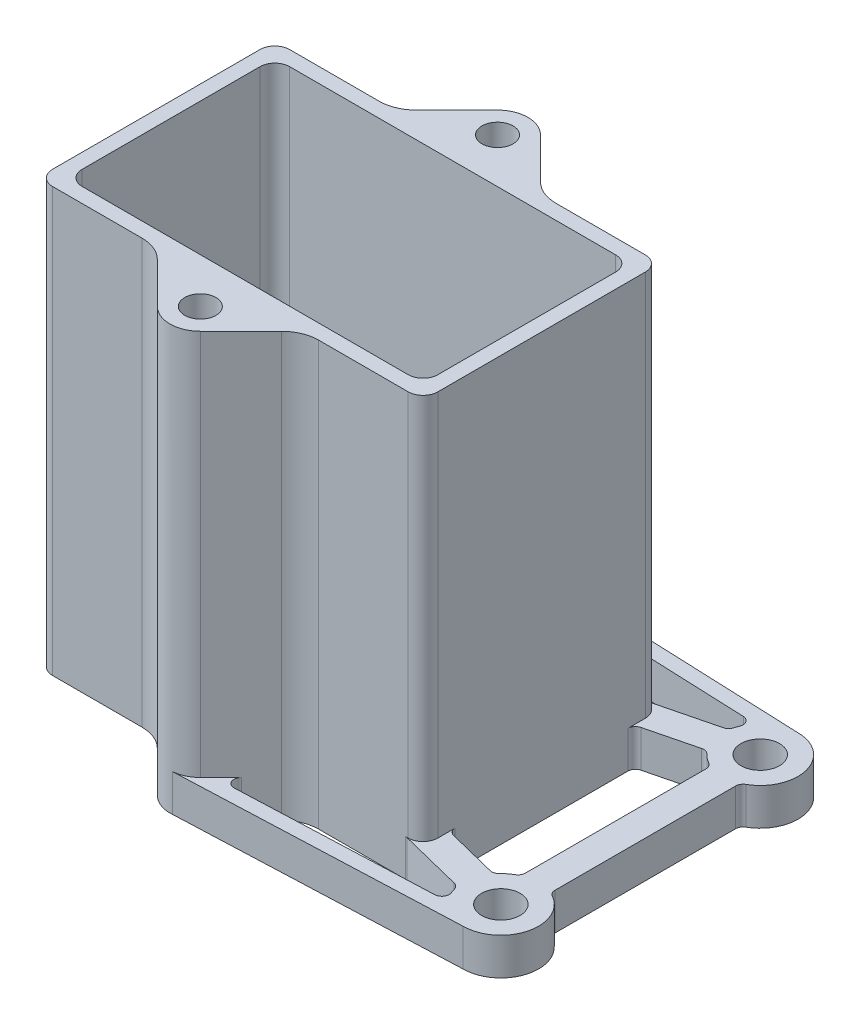
SolidWorks part; units mm, degrees
ref_plane "Front Plane" through (0, 0, 0) normal (0, 0, 1) x (1, 0, 0)
ref_plane "Top Plane" through (0, 0, 0) normal (0, 1, 0) x (1, 0, 0)
ref_plane "Right Plane" through (0, 0, 0) normal (1, 0, 0) x (0, 0, -1)
sketch "Sketch1" plane through (0, 0, 0) normal (0, 1, 0) x (1, 0, 0)
  line L1 (-26, -16) -> (26, -16)
  line L2 (-26, -16) -> (-26, 16)
  line L3 (-26, 16) -> (26, 16)
  line L4 (26, -16) -> (26, 16)
  line L5 (-26, -16) -> (26, 16) construction
  line L6 (-26, 16) -> (26, -16) construction
  point P0 (0, 0)
  dimension "D1" = 32
  dimension "D2" = 52
extrude "Boss-Extrude1" add sketch "Sketch1" along normal blind 3
sketch "Sketch2" plane through (0, 3, 0) normal (0, 1, 0) x (1, 0, 0)
  line L0 (24, -14) -> (24, 14)
  line L1 (24, 14) -> (-24, 14)
  line L2 (-24, 14) -> (-24, -14)
  line L3 (-24, -14) -> (24, -14)
  line L4 (26, -16) -> (26, 16)
  line L5 (26, 16) -> (-26, 16)
  line L6 (-26, 16) -> (-26, -16)
  line L7 (-26, -16) -> (26, -16)
  line L8 (26, -16) -> (26, 16)
  line L9 (26, 16) -> (-26, 16)
  line L10 (-26, 16) -> (-26, -16)
  line L11 (-26, -16) -> (26, -16)
  dimension "D1" = 0
  dimension "D2" = 2
extrude "Boss-Extrude2" add sketch "Sketch2" along normal blind 54.15
sketch "Sketch3" plane through (0, 0, 0) normal (0, 1, 0) x (1, 0, 0)
  line L0 (0, 0) -> (0, 20.05) construction
  line L1 (-2.8991, 22.9491) -> (-9.8483, 16)
  line L2 (-9.8483, 16) -> (9.8483, 16)
  line L3 (9.8483, 16) -> (2.8991, 22.9491)
  line L4 (26, -16) -> (26, 16)
  line L5 (-26, -16) -> (26, -16)
  line L6 (-26, 16) -> (-26, -16)
  line L7 (26, 16) -> (-26, 16)
  line L8 (26, -16) -> (26, 16)
  line L9 (-26, -16) -> (26, -16)
  line L10 (-26, 16) -> (-26, -16)
  line L11 (26, 16) -> (-26, 16)
  arc A0 (2.8991, 22.9491) -> (-2.8991, 22.9491) centre (0, 20.05) ccw
  circle A1 centre (0, 20.05) radius 2.1
  dimension "D3" = 2
  dimension "D4" = 4.2
  dimension "D2" = 45
  dimension "D5" = 20.05
  dimension "D1" = 0
extrude "Boss-Extrude3" add sketch "Sketch3" along direction (0, -1, 0) on the side of the normal up to surface (57.15 mm away) contours L3 A0 L1 L2 A1 L11 region at (0, 0, -23.9368) up to face at (0, 57.15, 0)
mirror "Mirror1" about plane through (0, 0, 0) normal (0, 0, 1) of "Boss-Extrude3"
fillet "Fillet1" radius 2 8 edges at (-26, 28.575, 16) (-24, 30.075, 14) (24, 30.075, 14) (26, 28.575, 16) (24, 30.075, -14) (26, 28.575, -16) (-24, 30.075, -14) (-26, 28.575, -16)
sketch "Sketch4" plane through (-26, 0, 0) normal (-1, 0, 0) x (0, 0, 1)
  circle A0 centre (0, 12.7) radius 5
  point P2 (0, 0)
  dimension "D2" = 10
  dimension "D1" = 12.7
extrude "Cut-Extrude1" cut sketch "Sketch4" against normal up to surface (2 mm away) up to face at (-24, 30.075, 0)
sketch "Sketch5" plane through (0, 0, 0) normal (0, 1, 0) x (1, 0, 0)
  line L0 (0, 0) -> (38, 0) construction
  line L1 (38, 0) -> (38, 17.5) construction
  line L2 (38, 22.6) -> (0, 24.15)
  line L3 (40, -12.8085) -> (40, 12.8085)
  line L4 (38, -22.6) -> (0, -24.15)
  line L5 (3.8573, 21.991) -> (34.0766, 20.7584)
  line L6 (3.8573, -21.991) -> (34.0766, -20.7584)
  line L7 (36, -12.8085) -> (36, 12.8085)
  line L8 (24, 14) -> (38, 17.5) construction
  line L9 (24, -14) -> (38, -17.5) construction
  line L10 (23.7538, 16) -> (32.9635, 18.3024)
  line L11 (26, 12.4384) -> (33.9337, 14.4219)
  line L12 (26, -12.4384) -> (33.9337, -14.4219)
  line L13 (23.7538, -16) -> (32.9635, -18.3024)
  line L15 (-24, -16) -> (-9.8483, -16)
  line L16 (-26, 14) -> (-26, -14)
  line L17 (-9.8483, 16) -> (-24, 16)
  line L18 (-2.8991, 22.9491) -> (-9.8483, 16)
  line L19 (9.8483, 16) -> (2.8991, 22.9491)
  line L20 (24, 16) -> (9.8483, 16)
  line L21 (26, -14) -> (26, 14)
  line L22 (9.8483, -16) -> (24, -16)
  line L23 (2.8991, -22.9491) -> (9.8483, -16)
  line L24 (-9.8483, -16) -> (-2.8991, -22.9491)
  line L25 (-24, -16) -> (-9.8483, -16)
  line L26 (-26, 14) -> (-26, -14)
  line L27 (-9.8483, 16) -> (-24, 16)
  line L28 (-2.8991, 22.9491) -> (-9.8483, 16)
  line L29 (9.8483, 16) -> (2.8991, 22.9491)
  line L30 (24, 16) -> (9.8483, 16)
  line L31 (26, -14) -> (26, 14)
  line L32 (9.8483, -16) -> (24, -16)
  line L33 (2.8991, -22.9491) -> (9.8483, -16)
  line L34 (-9.8483, -16) -> (-2.8991, -22.9491)
  circle A0 centre (38, 17.5) radius 2.6
  circle A1 centre (38, -17.5) radius 2.6
  circle A2 centre (38, 17.5) radius 5.1
  circle A3 centre (38, -17.5) radius 5.1
  arc A4 (2.8991, 22.9491) -> (-2.8991, 22.9491) centre (0, 20.05) ccw construction
  arc A5 (-2.8991, -22.9491) -> (2.8991, -22.9491) centre (0, -20.05) ccw construction
  arc A12 (-26, -14) -> (-24, -16) centre (-24, -14) ccw
  arc A13 (-24, 16) -> (-26, 14) centre (-24, 14) ccw
  arc A14 (2.8991, 22.9491) -> (-2.8991, 22.9491) centre (0, 20.05) ccw
  arc A15 (26, 14) -> (24, 16) centre (24, 14) ccw
  arc A16 (24, -16) -> (26, -14) centre (24, -14) ccw
  arc A17 (-2.8991, -22.9491) -> (2.8991, -22.9491) centre (0, -20.05) ccw
  arc A18 (-26, -14) -> (-24, -16) centre (-24, -14) ccw
  arc A19 (-24, 16) -> (-26, 14) centre (-24, 14) ccw
  arc A20 (2.8991, 22.9491) -> (-2.8991, 22.9491) centre (0, 20.05) ccw
  arc A21 (26, 14) -> (24, 16) centre (24, 14) ccw
  arc A22 (24, -16) -> (26, -14) centre (24, -14) ccw
  arc A23 (-2.8991, -22.9491) -> (2.8991, -22.9491) centre (0, -20.05) ccw
  point P51 (0, 0)
  dimension "D2" = 5.2
  dimension "D3" = 2.5
  dimension "D1" = 35
  dimension "D4" = 12
  dimension "D6" = 2
  dimension "D7" = 4
  dimension "D8" = 4
  dimension "D5" = 0
extrude "Boss-Extrude4" add sketch "Sketch5" along normal blind 5 contours A20 L29 L5 A2 L2 | A21 L31 L11 A2 L10 L30 | A2 L2 A0 | A3 L3 A2 L7 | A22 L32 L13 A3 L12 L31 | L4 A3 A1 | A23 L4 A3 L6 L33 region at (19.002, 0, -22.4046) region at (41.5042, 0, -21.0042) region at (38, 0, 0) region at (29.3978, 0, -15.3754) region at (42.1346, 0, 14.7679) region at (19.002, 0, 22.4046) region at (29.3978, 0, 15.3754)
fillet "Fillet2" radius 1 16 edges at (36, 2.5, -12.8085) (33.9337, 2.5, -14.4219) (23.7538, 2.5, 16) (34.0766, 2.5, 20.7584) (32.9635, 2.5, 18.3024) (36, 2.5, 12.8085) (33.9337, 2.5, 14.4219) (3.8573, 2.5, 21.991) (3.8573, 2.5, -21.991) (32.9635, 2.5, -18.3024) (34.0766, 2.5, -20.7584) (23.7538, 2.5, -16) (26, 2.5, -12.4384) (26, 2.5, 12.4384) (40, 2.5, 12.8085) (40, 2.5, -12.8085)
fillet "Fillet3" radius 5 4 edges at (9.8483, 28.575, 16) (-9.8483, 28.575, 16) (-9.8483, 28.575, -16) (9.8483, 28.575, -16)
